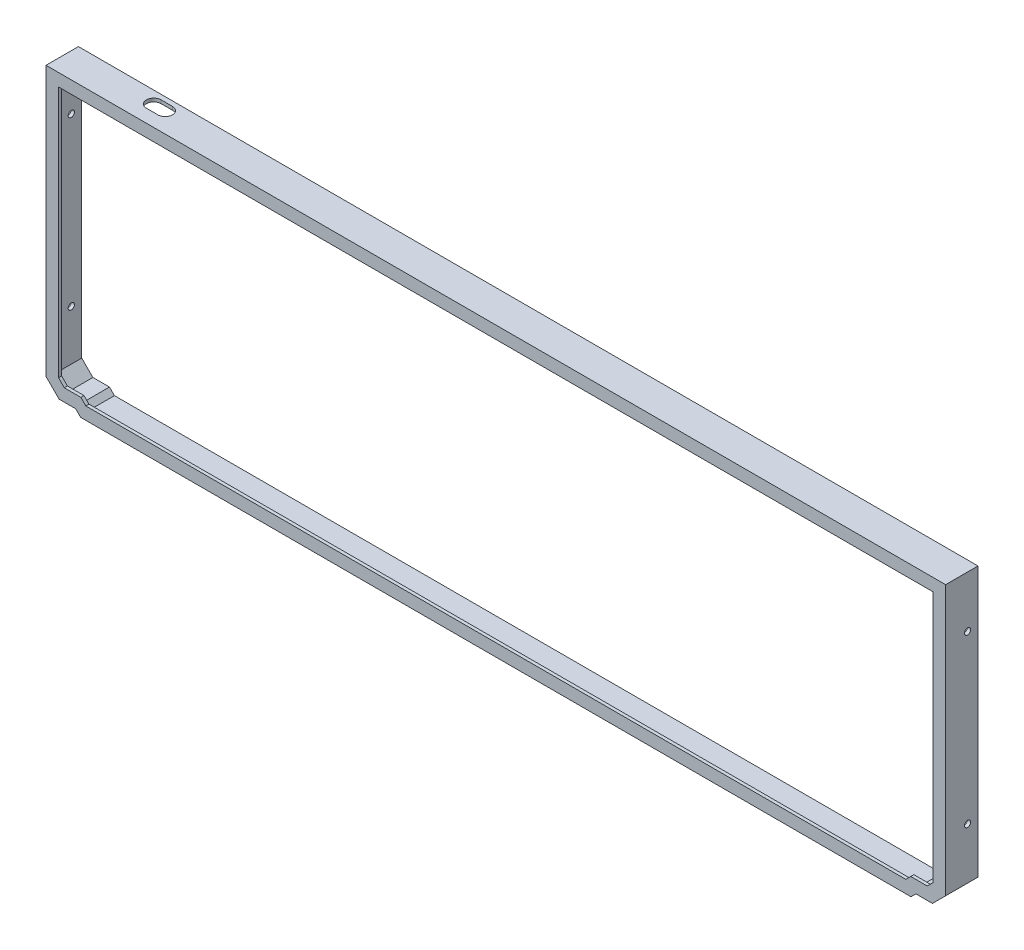
SolidWorks part; units mm, degrees
ref_plane "Přední rovina" through (0, 0, 0) normal (0, 0, 1) x (1, 0, 0)
ref_plane "Horní rovina" through (0, 0, 0) normal (0, 1, 0) x (1, 0, 0)
ref_plane "Pravá rovina" through (0, 0, 0) normal (1, 0, 0) x (0, 0, -1)
sketch "Skica1" plane through (0, 0, 0) normal (0, 0, 1) x (1, 0, 0)
  line L0 (0, 0) -> (428.28, 0) construction
  line L1 (0, 0) -> (0, -126.92) construction
  line L2 (428.28, 0) -> (428.28, -126.92) construction
  line L3 (0, -126.92) -> (5.3104, -132.2304) construction
  line L4 (428.28, -126.92) -> (422.9696, -132.2304) construction
  line L5 (5.3104, -132.2304) -> (13.2504, -132.2304) construction
  line L6 (422.9696, -132.2304) -> (415.0296, -132.2304) construction
  line L7 (13.2504, -132.2304) -> (15.6333, -134.6133) construction
  line L8 (415.0296, -132.2304) -> (412.6467, -134.6133) construction
  line L9 (412.6467, -134.6133) -> (15.6333, -134.6133) construction
  line L10 (-0.1, 0.1) -> (428.38, 0.1)
  line L11 (428.38, 0.1) -> (428.38, -126.9614)
  line L12 (428.38, -126.9614) -> (423.011, -132.3304)
  line L13 (423.011, -132.3304) -> (415.071, -132.3304)
  line L14 (415.071, -132.3304) -> (412.6881, -134.7133)
  line L15 (412.6881, -134.7133) -> (15.5919, -134.7133)
  line L16 (13.209, -132.3304) -> (15.5919, -134.7133)
  line L17 (5.269, -132.3304) -> (13.209, -132.3304)
  line L18 (-0.1, -126.9614) -> (5.269, -132.3304)
  line L19 (-0.1, 0.1) -> (-0.1, -126.9614)
  line L20 (-1.7, 1.7) -> (429.98, 1.7)
  line L21 (429.98, 1.7) -> (429.98, -127.6242)
  line L22 (429.98, -127.6242) -> (423.6738, -133.9304)
  line L23 (423.6738, -133.9304) -> (415.7338, -133.9304)
  line L24 (415.7338, -133.9304) -> (413.3508, -136.3133)
  line L25 (413.3508, -136.3133) -> (14.9292, -136.3133)
  line L26 (12.5462, -133.9304) -> (14.9292, -136.3133)
  line L27 (4.6062, -133.9304) -> (12.5462, -133.9304)
  line L28 (-1.7, -127.6242) -> (4.6062, -133.9304)
  line L29 (-1.7, 1.7) -> (-1.7, -127.6242)
  dimension "D1" = 428.28
  dimension "D2" = 126.92
  dimension "D3" = 126.92
  dimension "D4" = 7.51
  dimension "D5" = 7.51
  dimension "D6" = 135
  dimension "D7" = 135
  dimension "D8" = 7.94
  dimension "D9" = 7.94
  dimension "D10" = 3.37
  dimension "D11" = 3.37
  dimension "D12" = 135
  dimension "D13" = 0.1
  dimension "D14" = 1.6
extrude "Přidat vysunutím1" add sketch "Skica1" against normal blind 14.05
sketch "Skica2" plane through (0, 0, 0) normal (0, 0, 1) x (1, 0, 0)
  line L20 (4.3, -4.3) -> (4.3, -125.1389)
  line L21 (4.3, -125.1389) -> (7.0915, -127.9304)
  line L22 (7.0915, -127.9304) -> (15.0315, -127.9304)
  line L23 (15.0315, -127.9304) -> (17.4144, -130.3133)
  line L24 (17.4144, -130.3133) -> (410.8656, -130.3133)
  line L25 (410.8656, -130.3133) -> (413.2485, -127.9304)
  line L26 (413.2485, -127.9304) -> (421.1885, -127.9304)
  line L27 (421.1885, -127.9304) -> (423.98, -125.1389)
  line L28 (423.98, -125.1389) -> (423.98, -4.3)
  line L29 (423.98, -4.3) -> (4.3, -4.3)
  line L30 (4.3, -4.3) -> (4.3, -125.1389)
  line L31 (4.3, -125.1389) -> (7.0915, -127.9304)
  line L32 (7.0915, -127.9304) -> (15.0315, -127.9304)
  line L33 (15.0315, -127.9304) -> (17.4144, -130.3133)
  line L34 (17.4144, -130.3133) -> (410.8656, -130.3133)
  line L35 (410.8656, -130.3133) -> (413.2485, -127.9304)
  line L36 (413.2485, -127.9304) -> (421.1885, -127.9304)
  line L37 (421.1885, -127.9304) -> (423.98, -125.1389)
  line L38 (423.98, -125.1389) -> (423.98, -4.3)
  line L39 (423.98, -4.3) -> (4.3, -4.3)
  line L50 (-1.7, 1.7) -> (-1.7, -127.6242)
  line L51 (-1.7, -127.6242) -> (4.6062, -133.9304)
  line L52 (4.6062, -133.9304) -> (12.5462, -133.9304)
  line L53 (12.5462, -133.9304) -> (14.9292, -136.3133)
  line L54 (14.9292, -136.3133) -> (413.3508, -136.3133)
  line L55 (413.3508, -136.3133) -> (415.7338, -133.9304)
  line L56 (415.7338, -133.9304) -> (423.6738, -133.9304)
  line L57 (423.6738, -133.9304) -> (429.98, -127.6242)
  line L58 (429.98, -127.6242) -> (429.98, 1.7)
  line L59 (429.98, 1.7) -> (-1.7, 1.7)
  line L60 (-1.7, 1.7) -> (-1.7, -127.6242)
  line L61 (-1.7, -127.6242) -> (4.6062, -133.9304)
  line L62 (4.6062, -133.9304) -> (12.5462, -133.9304)
  line L63 (12.5462, -133.9304) -> (14.9292, -136.3133)
  line L64 (14.9292, -136.3133) -> (413.3508, -136.3133)
  line L65 (413.3508, -136.3133) -> (415.7338, -133.9304)
  line L66 (415.7338, -133.9304) -> (423.6738, -133.9304)
  line L67 (423.6738, -133.9304) -> (429.98, -127.6242)
  line L68 (429.98, -127.6242) -> (429.98, 1.7)
  line L69 (429.98, 1.7) -> (-1.7, 1.7)
  dimension "D1" = 6
  dimension "D2" = 0
extrude "Přidat vysunutím2" add sketch "Skica2" along normal blind 1.5
sketch "Skica3" plane through (0, 1.7, 0) normal (0, 1, 0) x (1, 0, 0)
  line L0 (-1.7, 8.25) -> (43.01, 8.25) construction
  line L1 (-1.7, 14.05) -> (-1.7, -1.5) construction
  line L2 (429.98, -1.5) -> (-1.7, -1.5) construction
  line L3 (45.76, 8.25) -> (40.26, 8.25) construction
  line L4 (45.76, 4.75) -> (40.26, 4.75)
  line L5 (45.76, 11.75) -> (40.26, 11.75)
  arc A0 (45.76, 4.75) -> (45.76, 11.75) centre (45.76, 8.25) ccw
  arc A1 (40.26, 11.75) -> (40.26, 4.75) centre (40.26, 8.25) ccw
  point P6 (40.26, 8.25)
  point P9 (43.01, 8.25)
  dimension "D1" = 9.75
  dimension "D2" = 44.71
  dimension "D3" = 2.75
  dimension "D4" = 7
extrude "Odebrat vysunutím1" cut sketch "Skica3" against normal up to surface (1.6 mm away) up to face at (214.14, 0.1, -7.025)
sketch "Skica4" plane through (-1.7, 0, 0) normal (-1, 0, 0) x (0, 0, 1)
  line L0 (-14.05, -62.9621) -> (1.5, -62.9621) construction
  line L1 (-14.05, 1.7) -> (-14.05, -127.6242) construction
  line L2 (1.5, 1.7) -> (1.5, -127.6242) construction
  circle A0 centre (-9.05, -22.9621) radius 1.5
  circle A1 centre (-9.05, -102.9621) radius 1.5
  dimension "D2" = 3
  dimension "D3" = 3
  dimension "D1" = 40
  dimension "D4" = 5
extrude "Odebrat vysunutím2" cut sketch "Skica4" against normal up to surface (431.68 mm away) up to face at (429.98, -62.9621, -6.275)
